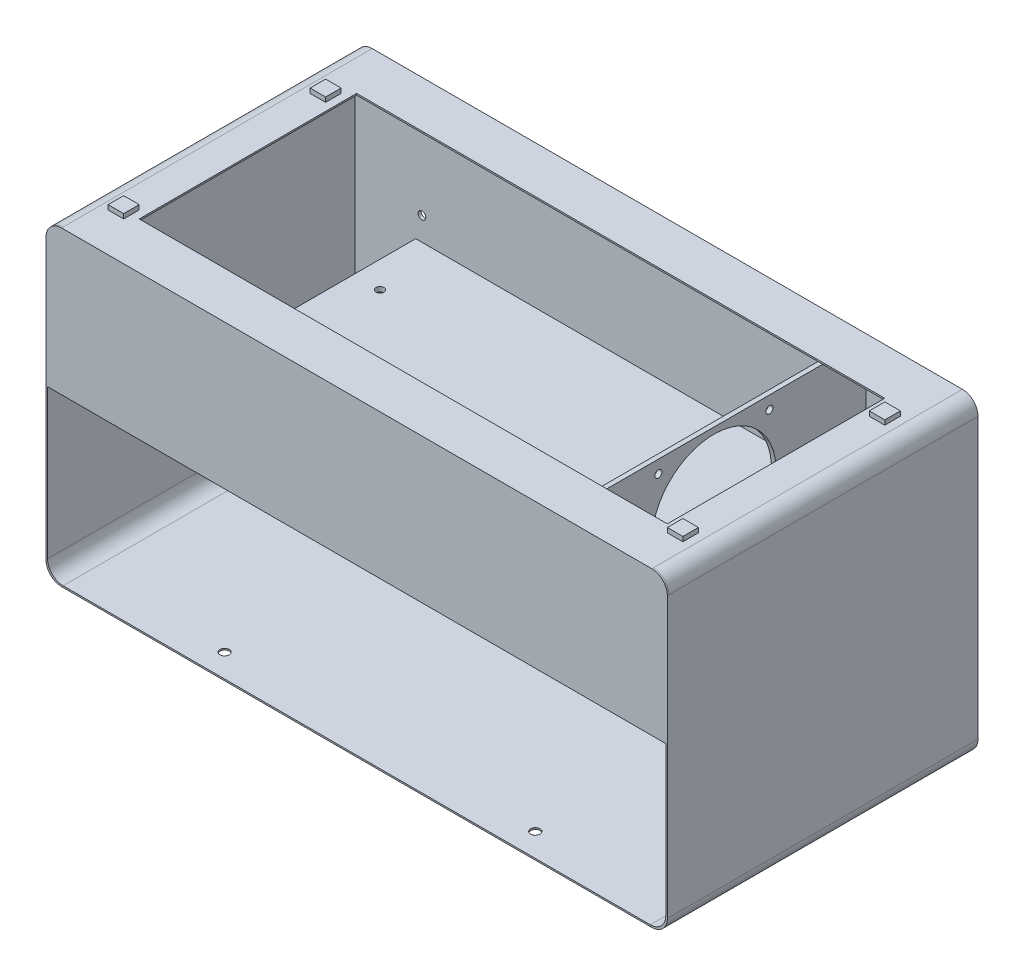
SolidWorks part; units mm, degrees
ref_plane "Front Plane" through (0, 0, 0) normal (0, 0, 1) x (1, 0, 0)
ref_plane "Top Plane" through (0, 0, 0) normal (0, 1, 0) x (1, 0, 0)
ref_plane "Right Plane" through (0, 0, 0) normal (1, 0, 0) x (0, 0, -1)
sketch "Sketch1" plane through (0, 0, 0) normal (0, 0, 1) x (1, 0, 0)
  line L1 (0, 0) -> (400, 0)
  line L2 (0, 0) -> (0, 200)
  line L3 (0, 200) -> (400, 200)
  line L4 (400, 0) -> (400, 200)
  dimension "D1" = 400
  dimension "D2" = 200
extrude "khung_trong" add sketch "Sketch1" along normal mid plane 200
sketch "Sketch2" plane through (0, 0, 100) normal (0, 0, 1) x (1, 0, 0)
  line L0 (400, 200) -> (0, 200) construction
  line L1 (1, 199) -> (399, 199)
  line L2 (1, 199) -> (1, 1)
  line L3 (1, 1) -> (399, 1)
  line L4 (399, 199) -> (399, 1)
  line L5 (0, 200) -> (0, 0) construction
  line L6 (400, 0) -> (400, 200) construction
  line L7 (0, 0) -> (400, 0) construction
  dimension "D1" = 1
  dimension "D2" = 1
  dimension "D3" = 1
  dimension "D4" = 1
extrude "do_day_1mm" cut sketch "Sketch2" against normal blind 198
fillet "Fillet_10mm_4_goc" radius 10 8 edges at (0, 0, 0) (1, 1, 1) (400, 0, 0) (399, 1, 1) (400, 200, 0) (399, 199, 1) (0, 200, 0) (1, 199, 1)
sketch "Sketch3" plane through (0, 0, -98) normal (0, 0, 1) x (1, 0, 0)
  line L0 (390, 200) -> (10, 200) construction
  line L1 (40, 110) -> (360, 110)
  line L2 (40, 110) -> (40, 107)
  line L3 (40, 107) -> (360, 107)
  line L4 (360, 110) -> (360, 107)
  line L5 (1, 189) -> (1, 11) construction
  dimension "D1" = 320
  dimension "D2" = 3
  dimension "D3" = 90
  dimension "D4" = 39
extrude "tran_gia" add sketch "Sketch3" along normal blind 198
sketch "Sketch5" plane through (0, 110, 0) normal (0, 1, 0) x (1, 0, 0)
  line L0 (360, 98) -> (40, 98) construction
  line L1 (327, 98) -> (330, 98)
  line L2 (327, 98) -> (327, -100)
  line L3 (327, -100) -> (330, -100)
  line L4 (330, 98) -> (330, -100)
  line L5 (360, -100) -> (40, -100) construction
  line L6 (360, -100) -> (360, 98) construction
  dimension "D1" = 3
  dimension "D2" = 30
extrude "gia_do_quat" add sketch "Sketch5" along normal blind 89
sketch "Sketch6" plane through (327, 0, 0) normal (-1, 0, 0) x (0, 0, 1)
  line L0 (-100, 200) -> (100, 200) construction
  circle A0 centre (0, 155) radius 40
  dimension "D1" = 80
  dimension "D2" = 45
extrude "lo_dat_quat" cut sketch "Sketch6" against normal blind 3
sketch "Sketch7" plane through (327, 0, 0) normal (-1, 0, 0) x (0, 0, 1)
  circle A0 centre (-35.75, 190.75) radius 2.3
  circle A1 centre (0, 155) radius 40 construction
  circle A2 centre (35.75, 190.75) radius 2.3
  circle A3 centre (35.75, 119.25) radius 2.3
  circle A4 centre (-35.75, 119.25) radius 2.3
  dimension "D1" = 4.6
  dimension "D2" = 35.75
  dimension "D3" = 35.75
  dimension "D4" = 2
  dimension "D5" = 2
extrude "co_dinh_quat" cut sketch "Sketch7" against normal blind 3
sketch "Sketch9" plane through (327, 0, 0) normal (-1, 0, 0) x (0, 0, 1)
  line L0 (100, 110) -> (-98, 110) construction
  line L1 (-68, 110) -> (-48, 110)
  line L2 (-68, 110) -> (-68, 130)
  line L3 (-68, 130) -> (-48, 130)
  line L4 (-48, 110) -> (-48, 130)
  line L5 (-98, 189) -> (-98, 11) construction
  line L6 (50, 110) -> (50, 130)
  line L7 (50, 110) -> (70, 110)
  line L8 (70, 110) -> (70, 130)
  line L9 (50, 130) -> (70, 130)
  dimension "D1" = 20
  dimension "D2" = 20
  dimension "D3" = 30
  dimension "D4" = 2
extrude "lo_thong_cho _den" cut sketch "Sketch9" against normal blind 3
sketch "Sketch10" plane through (0, 110, 0) normal (0, 1, 0) x (1, 0, 0)
  line L0 (330, 68) -> (327, 68) construction
  line L1 (330, -100) -> (330, 98) construction
  circle A0 centre (337, 58) radius 2.6
  circle A1 centre (337, -60) radius 2.6
  circle A2 centre (57, 58) radius 2.6
  circle A3 centre (57, -60) radius 2.6
  dimension "D1" = 10
  dimension "5.2" = 5.2
  dimension "D4" = 118
  dimension "D5" = 2
  dimension "D2" = 7
  dimension "D3" = 2
  dimension "D6" = 2
extrude "gia_do_den" cut sketch "Sketch10" against normal blind 3
sketch "Sketch12" plane through (0, 0, -98) normal (0, 0, 1) x (1, 0, 0)
  line L0 (360, 110) -> (330, 110) construction
  line L1 (330, 199) -> (330, 110) construction
  circle A0 centre (344, 125) radius 5
  dimension "D1" = 10
  dimension "D2" = 15
  dimension "D3" = 14
extrude "day_nguon_den_quat" cut sketch "Sketch12" against normal up to next
sketch "Sketch13" plane through (0, 0, -98) normal (0, 0, 1) x (1, 0, 0)
  line L0 (327, 110) -> (40, 110) construction
  circle A0 centre (44, 125) radius 2.5
  circle A1 centre (344, 125) radius 5 construction
  dimension "D1" = 5
  dimension "D3" = 300
  dimension "D2" = 15
extrude "day_nguon_den" cut sketch "Sketch13" against normal up to next
sketch "Sketch14" plane through (0, 1, 0) normal (0, 1, 0) x (1, 0, 0)
  line L0 (390, 100) -> (10, 100) construction
  line L1 (0, -100) -> (0, 100) construction
  circle A0 centre (100, 85) radius 3
  circle A1 centre (300, 85) radius 3
  circle A2 centre (300, -85) radius 3
  circle A3 centre (100, -85) radius 3
  dimension "D1" = 6
  dimension "D6" = 170
  dimension "D7" = 200
  dimension "D2" = 15
  dimension "D3" = 100
  dimension "D4" = 2
  dimension "D5" = 2
extrude "2_thanh_ray_tang1" cut sketch "Sketch14" against normal up to next
sketch "Sketch15" plane through (0, 0, -98) normal (0, 0, 1) x (1, 0, 0)
  line L0 (11, 1) -> (389, 1) construction
  line L1 (1, 189) -> (1, 11) construction
  circle A0 centre (121, 61) radius 4.1
  circle A1 centre (201, 61) radius 4.1
  circle A2 centre (281, 61) radius 4.1
  dimension "D1" = 8.2
  dimension "D2" = 60
  dimension "D3" = 120
  dimension "D4" = 3
extrude "gan_cam_bien" cut sketch "Sketch15" against normal up to next
sketch "Sketch16" plane through (0, 200, 0) normal (0, 1, 0) x (1, 0, 0)
  line L0 (0, -100) -> (0, 100) construction
  line L1 (30, 70) -> (370, 70)
  line L2 (30, 70) -> (30, -70)
  line L3 (30, -70) -> (370, -70)
  line L4 (370, 70) -> (370, -70)
  line L5 (390, 100) -> (10, 100) construction
  dimension "D1" = 340
  dimension "D2" = 30
  dimension "D3" = 30
  dimension "D4" = 140
extrude "nap_tham" cut sketch "Sketch16" against normal blind 1
sketch "Sketch18" plane through (0, 107, 0) normal (0, -1, 0) x (1, 0, 0)
  line L0 (400, 100) -> (400, -100) construction
  line L1 (1, 100) -> (400, 100)
  line L2 (1, 100) -> (1, 99)
  line L3 (1, 99) -> (400, 99)
  line L4 (400, 100) -> (400, 99)
  dimension "D1" = 1
extrude "che_tran" add sketch "Sketch18" against normal blind 93
fillet "Fillet4" radius 10 2 edges at (400, 200, 99.5) (1, 200, 99.5)
sketch "Sketch19" plane through (0, 200, 0) normal (0, 1, 0) x (1, 0, 0)
  line L1 (15, 65) -> (25, 65)
  line L2 (15, 65) -> (15, 55)
  line L3 (15, 55) -> (25, 55)
  line L4 (25, 65) -> (25, 55)
  line L5 (30, 70) -> (30, -70) construction
  line L6 (370, 70) -> (30, 70) construction
  line L7 (375, 65) -> (375, 55)
  line L8 (375, 65) -> (385, 65)
  line L9 (385, 65) -> (385, 55)
  line L10 (375, 55) -> (385, 55)
  line L11 (375, -65) -> (375, -75)
  line L12 (375, -65) -> (385, -65)
  line L13 (385, -65) -> (385, -75)
  line L14 (375, -75) -> (385, -75)
  line L15 (15, -65) -> (15, -75)
  line L16 (15, -65) -> (25, -65)
  line L17 (25, -65) -> (25, -75)
  line L18 (15, -75) -> (25, -75)
  dimension "D1" = 5
  dimension "D2" = 10
  dimension "D3" = 10
  dimension "D4" = 5
  dimension "D7" = 350
  dimension "D8" = 120
  dimension "D5" = 2
  dimension "D6" = 2
extrude "chot_co_dinh" add sketch "Sketch19" along normal blind 3
